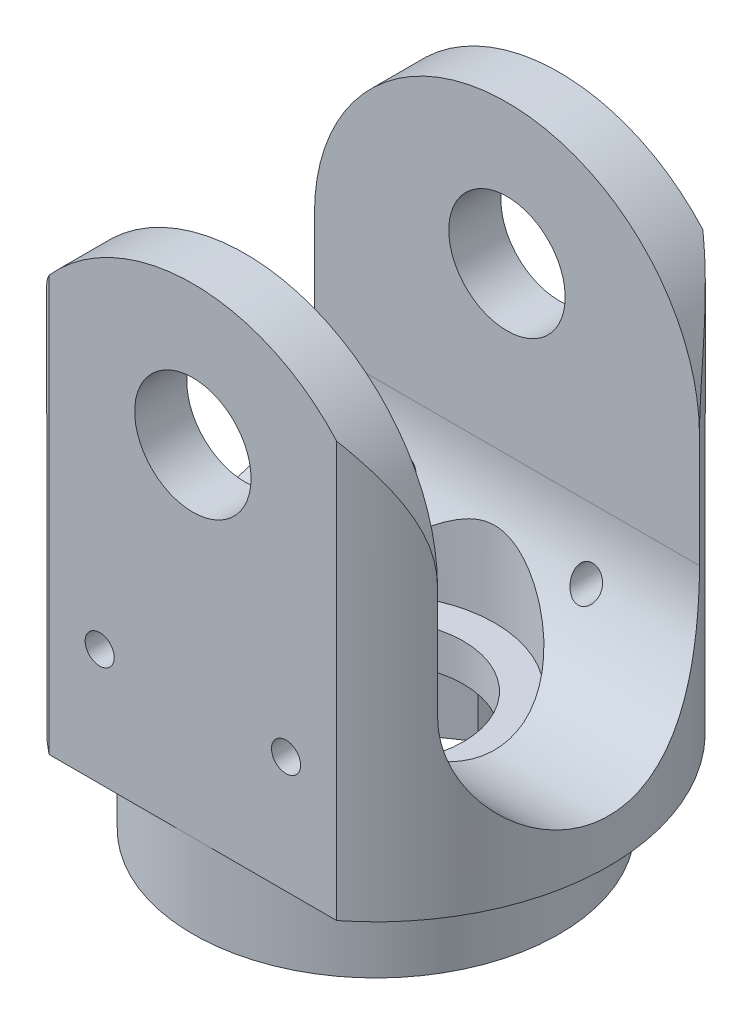
SolidWorks part; units mm, degrees
material "7075-T6 (SN)"
ref_plane "X-Y Datum" through (0, 0, 0) normal (0, 0, 1) x (1, 0, 0)
ref_plane "X-Z Datum" through (0, 0, 0) normal (0, 1, 0) x (1, 0, 0)
ref_plane "Y-Z Datum" through (0, 0, 0) normal (1, 0, 0) x (0, 0, -1)
sketch "Sketch1" plane through (0, 0, 0) normal (0, 1, 0) x (1, 0, 0)
  circle A0 centre (0, 0) radius 12.7
  dimension "D1" = 25.4
extrude "Boss-Extrude1" add sketch "Sketch1" along normal blind 15.367 and the other way blind 15.367
ref_plane "Plane2" through (0, 0, 9.9886) normal (0, 0, 1) x (1, 0, 0)
sketch "Sketch4" plane through (0, 0, 9.9886) normal (0, 0, 1) x (1, 0, 0)
  line L1 (-12.7, 15.367) -> (12.7, 15.367)
  line L2 (-12.7, 15.367) -> (-12.7, -15.367)
  line L3 (-12.7, -15.367) -> (12.7, -15.367)
  line L4 (12.7, 15.367) -> (12.7, -15.367)
extrude "Cut-Extrude2" cut sketch "Sketch4" along normal through all
mirror "Mirror2" about plane through (0, 0, 0) normal (0, 0, 1) of "Cut-Extrude2"
sketch "Sketch5" plane through (0, 0, 0) normal (1, 0, 0) x (0, 0, -1)
  line L0 (9.9886, 15.367) -> (-9.9886, 15.367) construction
  line L1 (-7.1437, 15.367) -> (7.1437, 15.367)
  line L2 (-7.1437, 15.367) -> (-7.1437, -1.27)
  line L3 (-7.1437, -1.27) -> (7.1438, -1.27)
  line L4 (7.1437, 15.367) -> (7.1438, -1.27)
  line L5 (0, 13.97) -> (0, -13.97) construction
  line L6 (0, -8.4138) -> (0, 15.367) construction
  arc A0 (-7.1437, -1.27) -> (7.1438, -1.27) centre (0, -1.27) ccw
  dimension "D3" = 16.637
  dimension "D4" = 23.7808
  dimension "D1" = 14.2875
  dimension "D2" = 7.1437
extrude "Cut-Extrude3" cut sketch "Sketch5" against normal through all both and the other way through all contours L6 A0 L3 | A0 L6 L3 | L2 L1 L4 L3 region at (0, -4.3019, 3.0319) region at (0, -4.3019, -3.0319)
sketch "Sketch6" plane through (0, 0, 9.9886) normal (0, 0, 1) x (1, 0, 0)
  line L0 (0, -43.0151) -> (0, 43.0151) construction
  line L1 (-7.8434, 15.367) -> (7.8434, 15.367) construction
  line L2 (10.5004, 4.8666) -> (14.8497, 4.8666)
  line L3 (-10.5004, 4.8666) -> (-14.8497, 4.8666)
  circle A0 centre (0, 4.8666) radius 10.5004
  arc A1 (14.8497, 4.8666) -> (-14.8497, 4.8666) centre (0, 4.8666) ccw
  line M2 (7.8434, 15.367) -> (-7.8434, 15.367)
  line M3 (-7.8434, 15.367) -> (-7.8434, -15.367)
  line M5 (7.8434, -15.367) -> (7.8434, 15.367)
  dimension "D1" = 21.0007
extrude "Cut-Extrude4" cut sketch "Sketch6" against normal through all contours L2 A1 L3 A0 M3 M2 M5 | A0 M2 M3 | A0 M5 M2 region at (10.124, 8.7197, 9.9886) region at (5.9543, 14.3505, 9.9886) region at (-5.9543, 14.3505, 9.9886)
sketch "Sketch7" plane through (0, -15.367, 0) normal (0, -1, 0) x (1, 0, 0)
  circle A0 centre (0, 0) radius 4.7625
  dimension "D1" = 9.525
extrude "Cut-Extrude5" cut sketch "Sketch7" against normal through all
sketch "Sketch9" plane through (0, -15.367, 0) normal (0, -1, 0) x (1, 0, 0)
  circle A0 centre (0, 0) radius 9.9822
  circle A1 centre (0, 0) radius 17.8528
  dimension "D1" = 19.9644
extrude "Cut-Extrude6" cut sketch "Sketch9" against normal blind 4.572
ref_plane "Plane3" through (0, 15.367, 0) normal (0, 1, 0) x (1, 0, 0)
sketch "Sketch10" plane through (0, 15.367, 0) normal (0, 1, 0) x (1, 0, 0)
  circle A0 centre (0, 0) radius 6.477
  dimension "D1" = 12.954
extrude "Cut-Extrude7" cut sketch "Sketch10" against normal blind 24.257
sketch "Sketch11" plane through (0, 0, 9.9886) normal (0, 0, 1) x (1, 0, 0)
  line L0 (-9.9822, -10.795) -> (9.9822, -10.795) construction
  line L1 (0, 7.747) -> (0, 0) construction
  circle A0 centre (0, 7.747) radius 3.175
  dimension "D1" = 6.35
  dimension "D2" = 18.542
extrude "Cut-Extrude8" cut sketch "Sketch11" against normal through all
sketch "Sketch12" plane through (0, 0, -9.9886) normal (0, 0, -1) x (-1, 0, 0)
  line L0 (-7.8434, -10.795) -> (7.8434, -10.795) construction
  line L1 (7.8434, 11.848) -> (7.8434, -10.795) construction
  line L2 (-7.8434, -10.795) -> (-7.8434, 11.848) construction
  circle A0 centre (5.0811, -4.445) radius 0.7938
  circle A1 centre (-5.0811, -4.445) radius 0.7938
  point P6 (-5.8749, -4.445)
  point P7 (5.8749, -4.445)
  dimension "D1" = 1.5875
  dimension "D2" = 1.5875
  dimension "D3" = 6.35
  dimension "D4" = 6.35
  dimension "D5" = 1.9685
  dimension "D6" = 1.9685
extrude "Cut-Extrude9" cut sketch "Sketch12" against normal through all both and the other way through all
sketch "Sketch13" plane through (0, -15.367, 0) normal (0, -1, 0) x (1, 0, 0)
  line L0 (-0.2399, -7.9974) -> (7.5971, -2.5099)
  line L1 (4.5892, -6.554) -> (0, 0) construction
  line L2 (-2.6525, 0) -> (2.3493, 0)
  circle A0 centre (0, 0) radius 8.001
  dimension "D1" = 16.002
  dimension "D2" = 35
  dimension "D3" = 6.4135
extrude "Cut-Extrude10" [suppressed] cut sketch "Sketch13" against normal blind 4.445
sketch "Sketch14" [suppressed] plane through (0, -15.367, 0) normal (0, -1, 0) x (1, 0, 0)
  line L0 (0, 0) -> (-0.2399, -7.9974) construction
  line L1 (0, 0) -> (7.5971, -2.5099) construction
  circle A0 centre (-0.217, -7.2354) radius 1.5875
  circle A1 centre (6.8736, -2.2708) radius 1.5875
  dimension "D1" = 3.175
  dimension "D2" = 3.175
  dimension "D3" = 0.762
  dimension "D4" = 0.762
extrude "Cut-Extrude11" [suppressed] cut sketch "Sketch14" against normal up to surface (4.445 mm away) up to face at (0, -15.367, -4.7625)
sketch "Sketch15" plane through (0, -15.367, 0) normal (0, -1, 0) x (1, 0, 0)
  line L0 (-7.5971, -2.5099) -> (0.2399, -7.9974)
  line L1 (-4.5892, -6.554) -> (0, 0) construction
  line L2 (0.0088, 0) -> (5.0106, 0)
  circle A0 centre (0, 0) radius 8.001
  circle A1 centre (0, 0) radius 9.9822 construction
  dimension "D3" = 16.002
  dimension "D1" = 35
  dimension "D2" = 6.4135
extrude "Cut-Extrude12" cut sketch "Sketch15" against normal blind 4.445 contours L0 A0 region at (0.2194, -15.367, 0.3134)
sketch "Sketch16" plane through (0, -15.367, 0) normal (0, -1, 0) x (1, 0, 0)
  line L0 (0, 0) -> (-7.5971, -2.5099) construction
  line L1 (0, 0) -> (0.2399, -7.9974) construction
  circle A0 centre (-6.8736, -2.2708) radius 1.5875
  circle A1 centre (0.217, -7.2354) radius 1.5875
  dimension "D1" = 3.175
  dimension "D2" = 0.762
  dimension "D3" = 0.762
extrude "Cut-Extrude13" cut sketch "Sketch16" against normal up to surface (4.445 mm away) up to face at (0, -10.922, -4.7625)
sketch "Pick Up Point" plane through (0, 0, 0) normal (0, 0, 1) x (1, 0, 0)
  point P0 (0, 7.747)
ref_plane "Plane4" through (0, 15.367, -7.1437) normal (0, 1, 0) x (1, 0, 0)
sketch "Sketch20" plane through (0, 15.367, -7.1437) normal (0, 1, 0) x (1, 0, 0)
  circle A0 centre (0, -7.1437) radius 12.7
  point P3 (0, 5.5562)
  point P4 (0, -19.8438)
  point P6 (0, -7.1437)
  dimension "D1" = 25.4
ref_plane "Plane5" through (0, -15.367, 0) normal (0, -1, 0) x (-1, 0, 0)
sketch "Sketch21" plane through (0, -15.367, 0) normal (0, -1, 0) x (-1, 0, 0)
  point P0 (0, 0)
ref_point "Point1"
ref_point "Point2"
ref_point "Point3"
ref_point "Point4"
sketch "Sketch19" plane through (0, -10.922, 0) normal (0, -1, 0) x (1, 0, 0)
  line L0 (1.693, -7.8198) -> (-7.9273, -1.0834) construction
  arc A0 (1.693, -7.8198) -> (-7.9273, -1.0834) centre (0, 0) ccw construction
ref_point "Point5"
ref_axis "Axis1" through (0, -10.922, 0) along (0, -1, 0)
sketch "Sketch22" plane through (0, 0, 9.9886) normal (0, 0, 1) x (1, 0, 0)
  arc A0 (7.8434, 11.848) -> (-7.8434, 11.848) centre (0, 4.8666) ccw construction
  point P0 (0, 15.367)
